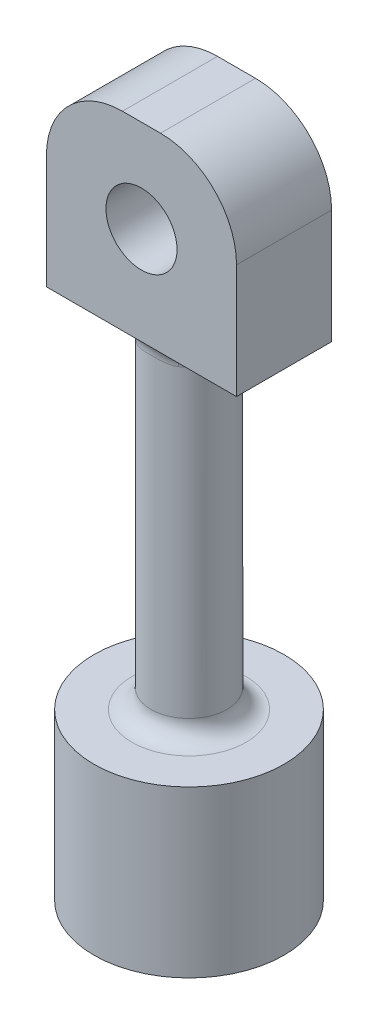
SolidWorks part; units mm, degrees
ref_plane "Front Plane" through (0, 0, 0) normal (0, 0, 1) x (1, 0, 0)
ref_plane "Top Plane" through (0, 0, 0) normal (0, 1, 0) x (1, 0, 0)
ref_plane "Right Plane" through (0, 0, 0) normal (1, 0, 0) x (0, 0, -1)
sketch "Sketch2" plane through (0, 0, 0) normal (0, 1, 0) x (1, 0, 0)
  circle A0 centre (0, 0) radius 6.35
extrude "Boss-Extrude1" add sketch "Sketch2" along normal blind 11.049
sketch "Sketch3" plane through (0, 11.049, 0) normal (0, 1, 0) x (1, 0, 0)
  circle A0 centre (0, 0) radius 2.54
extrude "Boss-Extrude2" add sketch "Sketch3" along normal blind 22.86
sketch "Sketch4" plane through (0, 33.909, 0) normal (0, 1, 0) x (1, 0, 0)
  line L1 (-6.35, -3.175) -> (6.35, -3.175)
  line L2 (-6.35, -3.175) -> (-6.35, 3.175)
  line L3 (-6.35, 3.175) -> (6.35, 3.175)
  line L4 (6.35, -3.175) -> (6.35, 3.175)
  line L5 (-6.35, -3.175) -> (6.35, 3.175) construction
  line L6 (-6.35, 3.175) -> (6.35, -3.175) construction
  point P0 (0, 0)
  dimension "D1" = 6.35
  dimension "D2" = 12.7
extrude "Boss-Extrude3" add sketch "Sketch4" along normal blind 12.7
sketch "Sketch5" plane through (0, 0, 3.175) normal (0, 0, 1) x (1, 0, 0)
  circle A0 centre (0, 40.427) radius 2.3749
extrude "Cut-Extrude2" cut sketch "Sketch5" against normal blind 12.7 contours A0
fillet "Fillet1" radius 5.08 2 edges at (6.35, 46.609, 0) (-6.35, 46.609, 0)
fillet "Fillet2" radius 1.27 2 edges at (0, 11.049, 2.54) (0, 33.909, 2.54)
